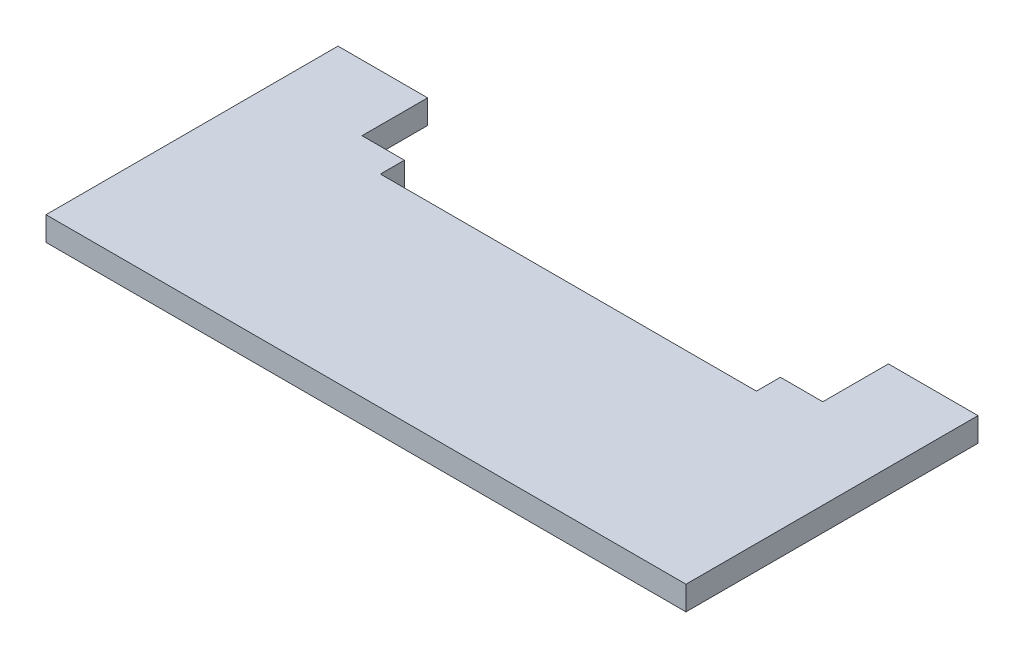
SolidWorks part; units mm, degrees
ref_plane "Front Plane" through (0, 0, 0) normal (0, 0, 1) x (1, 0, 0)
ref_plane "Top Plane" through (0, 0, 0) normal (0, 1, 0) x (1, 0, 0)
ref_plane "Right Plane" through (0, 0, 0) normal (1, 0, 0) x (0, 0, -1)
sketch "Sketch1" plane through (0, 0, 0) normal (0, 1, 0) x (1, 0, 0)
  line L0 (40, -36.5) -> (40, 0) construction
  line L1 (0, 0) -> (80, 0) construction
  line L2 (0, 0) -> (0, -36.5)
  line L3 (0, -36.5) -> (80, -36.5)
  line L4 (80, 0) -> (80, -36.5)
  line L5 (16.5, 0) -> (16.5, -3) construction
  line L6 (16.5, -3) -> (0, -3) construction
  line L7 (11.2, 0) -> (11.2, -8.2)
  line L8 (11.2, -8.2) -> (16.5, -8.2)
  line L9 (16.5, -8.2) -> (16.5, -11.2)
  line L10 (0, -11.2) -> (80, -11.2) construction
  line L12 (3, -3) -> (77, -3) construction
  line L13 (16.5, -8.2) -> (16.5, -11.2) construction
  line L14 (11.2, -8.2) -> (11.2, -3) construction
  line L15 (11.2, -8.2) -> (16.5, -8.2) construction
  line L16 (16.5, -11.2) -> (0, -11.2) construction
  line L17 (63.5, -8.2) -> (63.5, -11.2)
  line L18 (68.8, -8.2) -> (63.5, -8.2)
  line L19 (68.8, 0) -> (68.8, -8.2)
  line L20 (63.5, -11.2) -> (16.5, -11.2)
  line L21 (11.2, 0) -> (0, 0)
  line L22 (80, 0) -> (68.8, 0)
sketch "Sketch2" plane through (0, 0, 0) normal (0, 0, 1) x (1, 0, 0)
  line L1 (80, 0) -> (0, 0)
  line L2 (80, 0) -> (80, -3)
  line L3 (80, -3) -> (0, -3)
  line L4 (0, 0) -> (0, -3)
extrude "Boss-Extrude1" add sketch "Sketch1" against normal up to vertex (3 mm away) up to point (0, -3, 0)
